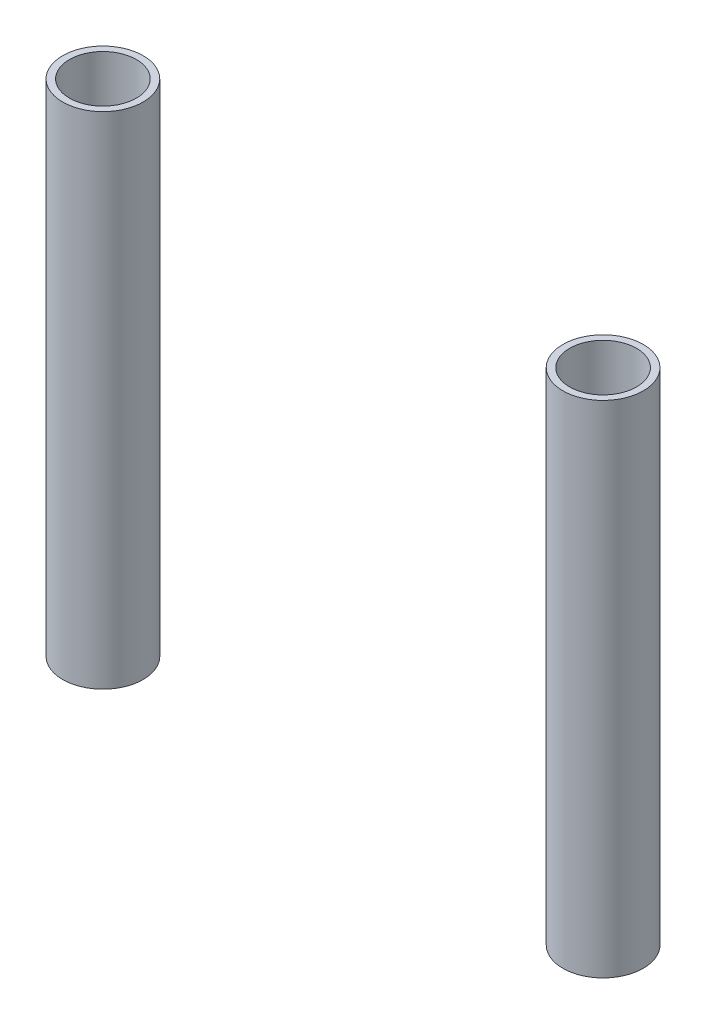
SolidWorks part; units mm, degrees
ref_plane "Front" through (0, 0, 0) normal (0, 0, 1) x (1, 0, 0)
ref_plane "Top" through (0, 0, 0) normal (0, 1, 0) x (1, 0, 0)
ref_plane "Right" through (0, 0, 0) normal (1, 0, 0) x (0, 0, -1)
sketch "Sketch1" plane through (0, 0, 0) normal (0, 1, 0) x (1, 0, 0)
  line L0 (50, 0) -> (-50, 0) construction
  line L1 (0, 0) -> (0, 6.5479) construction
  circle A0 centre (-50, 0) radius 8.039
  circle A1 centre (50, 0) radius 6.6928
  circle A2 centre (-50, 0) radius 6.6928
  circle A3 centre (50, 0) radius 8.039
  point P4 (0, 0)
  dimension "D1" = 100
  dimension "D2" = 16.078
  dimension "D3" = 1.3462
extrude "Boss-Extrude1" add sketch "Sketch1" along normal blind 100
